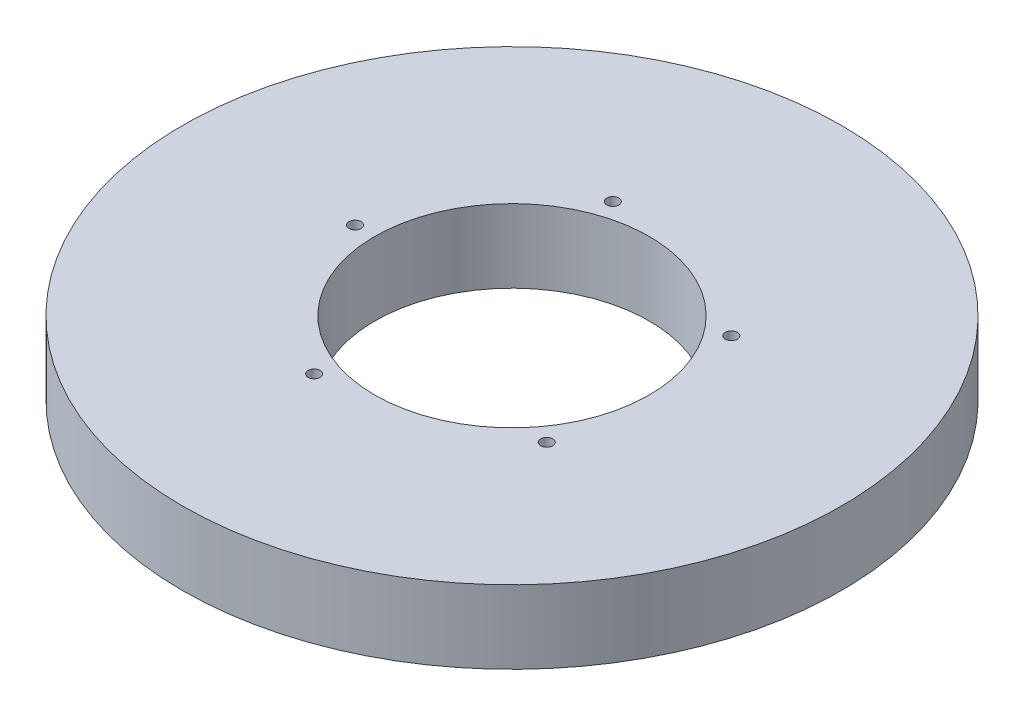
SolidWorks part; units mm, degrees
ref_plane "Front Plane" through (0, 0, 0) normal (0, 0, 1) x (1, 0, 0)
ref_plane "Top Plane" through (0, 0, 0) normal (0, 1, 0) x (1, 0, 0)
ref_plane "Right Plane" through (0, 0, 0) normal (1, 0, 0) x (0, 0, -1)
sketch "Sketch1" plane through (0, 0, 0) normal (0, 1, 0) x (1, 0, 0)
  circle A0 centre (0, 0) radius 90
  dimension "FLANGE_OD" = 180
extrude "Boss-Extrude1" add sketch "Sketch1" along normal blind 20
sketch "Sketch2" plane through (0, 0, 0) normal (0, 1, 0) x (1, 0, 0)
  circle A0 centre (0, 0) radius 37.5
  dimension "BORE_D" = 75
extrude "Cut-Extrude1" cut sketch "Sketch2" along normal through all
sketch "Sketch3" plane through (0, 20, 0) normal (0, 1, 0) x (1, 0, 0)
  circle A0 centre (0, 0) radius 42.8749 construction
  circle A1 centre (-42.8749, 0) radius 1.6482
  dimension "BOLT_D" = 3.2965
  dimension "BOLT_PCD" = 85.7498
extrude "Cut-Extrude2" cut sketch "Sketch3" against normal blind 19.4108
pattern_circular "CirPattern1" count 5 over 360 about axis through (0, 0, 0) along (0, 1, 0) of "Cut-Extrude2"
